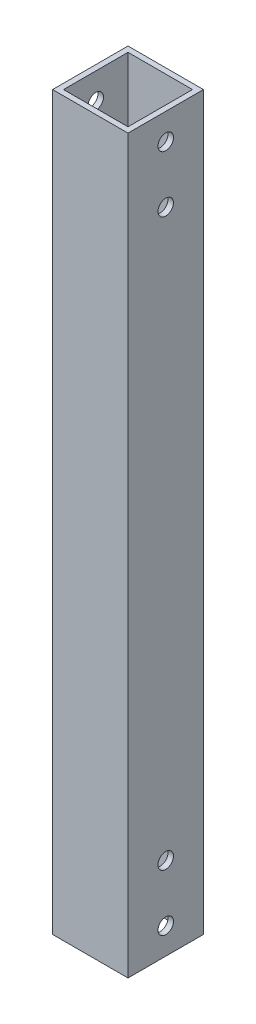
SolidWorks part; units mm, degrees
ref_plane "Front Plane" through (0, 0, 0) normal (0, 0, 1) x (1, 0, 0)
ref_plane "Top Plane" through (0, 0, 0) normal (0, 1, 0) x (1, 0, 0)
ref_plane "Right Plane" through (0, 0, 0) normal (1, 0, 0) x (0, 0, -1)
sketch "Sketch1" plane through (0, 0, 0) normal (0, 1, 0) x (1, 0, 0)
  line L0 (1.45, 18.55) -> (18.55, 18.55)
  line L1 (0, 0) -> (20, 0)
  line L2 (0, 0) -> (0, 20)
  line L3 (0, 20) -> (20, 20)
  line L4 (20, 0) -> (20, 20)
  line L5 (18.55, 1.45) -> (18.55, 18.55)
  line L6 (1.45, 1.45) -> (18.55, 1.45)
  line L7 (1.45, 1.45) -> (1.45, 18.55)
  dimension "D1" = 20
  dimension "D2" = 1.45
extrude "Boss-Extrude1" add sketch "Sketch1" along normal blind 194
sketch "Sketch2" plane through (0, 0, 0) normal (-1, 0, 0) x (0, 0, 1)
  line L0 (-20, 194) -> (-20, 0) construction
  line L1 (-20, 194) -> (0, 194) construction
  line L2 (-20, 0) -> (0, 0) construction
  circle A0 centre (-10, 187) radius 2.05
  circle A1 centre (-10, 172) radius 2.05
  circle A2 centre (-10, 22) radius 2.05
  circle A3 centre (-10, 7) radius 2.05
  dimension "D1" = 4.1
  dimension "D2" = 15
  dimension "D3" = 15
  dimension "D4" = 10
  dimension "D5" = 7
  dimension "D6" = 7
extrude "Cut-Extrude1" cut sketch "Sketch2" against normal through all
